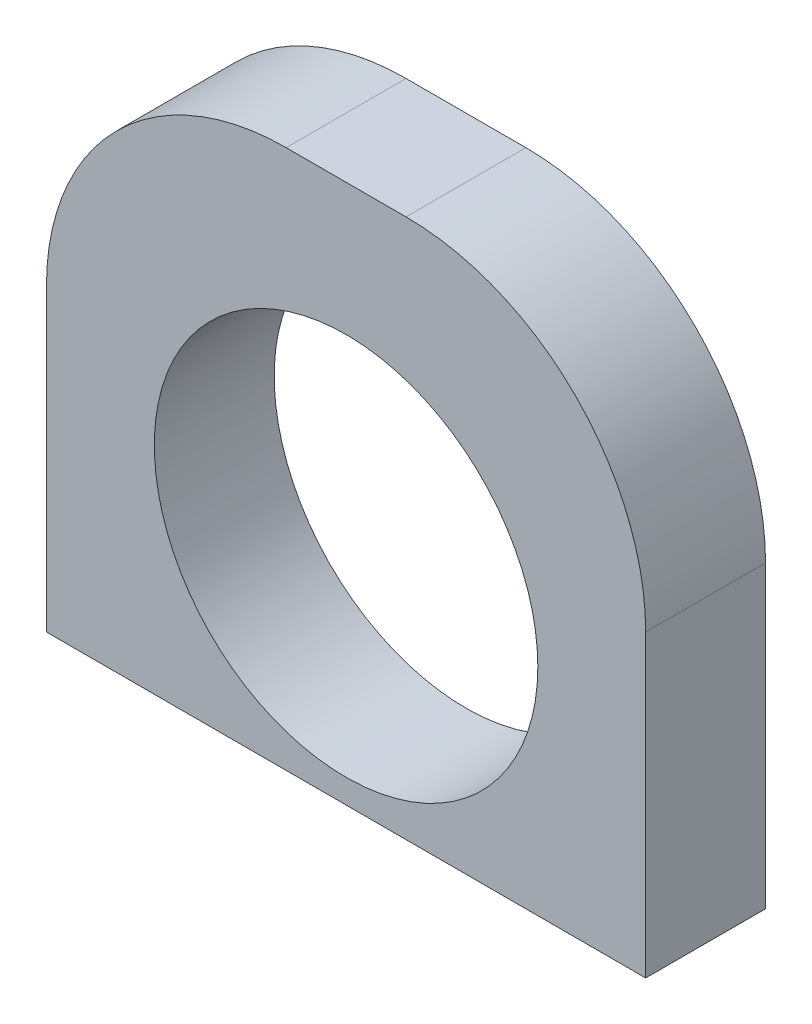
SolidWorks part; units mm, degrees
ref_plane "Front Plane" through (0, 0, 0) normal (0, 0, 1) x (1, 0, 0)
ref_plane "Top Plane" through (0, 0, 0) normal (0, 1, 0) x (1, 0, 0)
ref_plane "Right Plane" through (0, 0, 0) normal (1, 0, 0) x (0, 0, -1)
sketch "Sketch1" plane through (0, 0, 0) normal (0, 0, 1) x (1, 0, 0)
  line L4 (-15.875, -14.2875) -> (15.875, -14.2875)
  line L5 (-15.875, -14.2875) -> (-15.875, 1.5875)
  line L6 (-3.175, 14.2875) -> (3.175, 14.2875)
  line L7 (15.875, -14.2875) -> (15.875, 1.5875)
  line L8 (-15.875, -14.2875) -> (15.875, 14.2875) construction
  line L9 (-15.875, 14.2875) -> (15.875, -14.2875) construction
  circle A1 centre (0, -2.8575) radius 10.16
  arc A2 (3.175, 14.2875) -> (15.875, 1.5875) centre (3.175, 1.5875) cw
  arc A3 (-15.875, 1.5875) -> (-3.175, 14.2875) centre (-3.175, 1.5875) cw
  point P0 (0, 0)
  point P4 (0, 0)
  dimension "D1" = 31.75
  dimension "D3" = 20.32
  dimension "D4" = 12.7
  dimension "D2" = 28.575
  dimension "D5" = 11.43
extrude "Boss-Extrude3" add sketch "Sketch1" along normal blind 6.35
